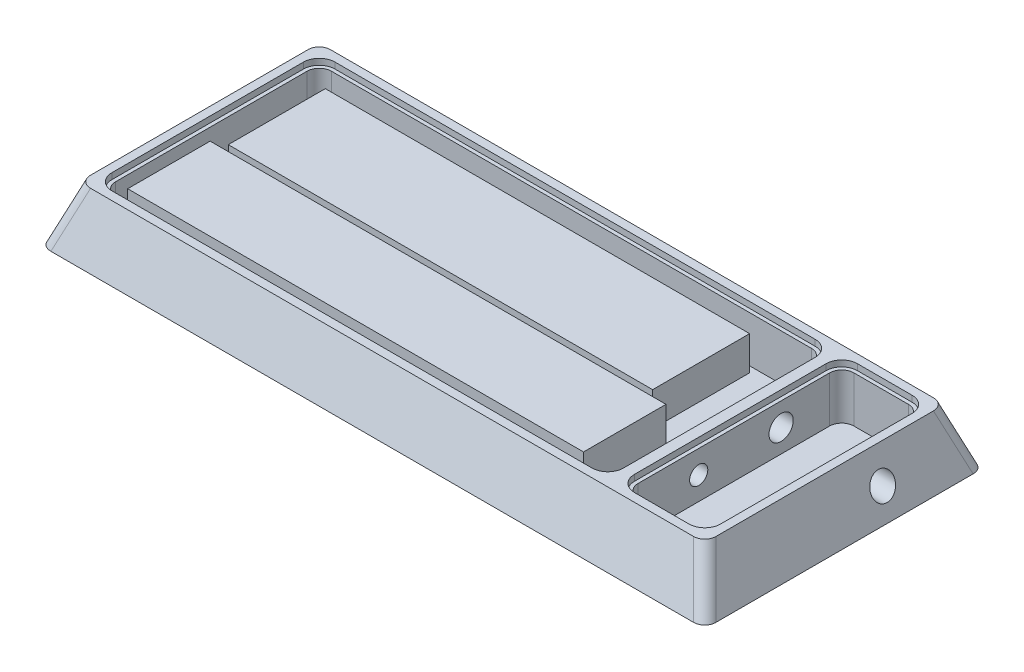
SolidWorks part; units mm, degrees
ref_plane "Front Plane" through (0, 0, 0) normal (0, 0, 1) x (1, 0, 0)
ref_plane "Top Plane" through (0, 0, 0) normal (0, 1, 0) x (1, 0, 0)
ref_plane "Right Plane" through (0, 0, 0) normal (1, 0, 0) x (0, 0, -1)
sketch "Sketch2" plane through (0, 0, 0) normal (0, 1, 0) x (1, 0, 0)
  line L0 (168, -89) -> (168, 89)
  line L1 (-248, -89) -> (168, -89)
  line L2 (-248, -89) -> (-248, 89)
  line L3 (-248, 89) -> (168, 89)
  line L4 (248, -89) -> (248, 89)
  line L5 (-248, -89) -> (248, 89) construction
  line L6 (-248, 89) -> (248, -89) construction
  line L7 (-238, -79) -> (138, -79)
  line L8 (-238, -79) -> (-238, -11)
  line L9 (-238, -11) -> (138, -11)
  line L10 (138, -79) -> (138, -11)
  line L11 (-238, 4) -> (112, 4)
  line L12 (-238, 4) -> (-238, 84)
  line L13 (-238, 84) -> (112, 84)
  line L14 (112, 4) -> (112, 84)
  line L15 (-258, 99) -> (258, 99)
  line L16 (258, -99) -> (258, 99)
  line L17 (-258, -99) -> (258, -99)
  line L18 (-258, -99) -> (-258, 99)
  line L19 (183, -89) -> (183, 89)
  line L20 (183, 89) -> (248, 89)
  line L21 (-248, 89) -> (248, 89) construction
  line L22 (183, -89) -> (248, -89)
  line L23 (-248, -89) -> (248, -89) construction
  point P0 (0, 0)
  point P14 (-238, -45)
  point P15 (-238, 44)
  dimension "D1" = 178
  dimension "D3" = 376
  dimension "D4" = 68
  dimension "D5" = 350
  dimension "D6" = 80
  dimension "D7" = 10
  dimension "D8" = 10
  dimension "D9" = 15
  dimension "D2" = 416
  dimension "D10" = 80
  dimension "D11" = 10
  dimension "D12" = 15
extrude "Boss-Extrude2" add sketch "Sketch2" along normal blind 45 contours L18 L17 L16 L15 L22 L19 L20 L4 L2 L3 L0 L1 region at (0, 0, -93.4732)
draft "Draft3" type of draft neutral plane draft angle 20 faces to draft 4 face at (0, 22.5, -99) face at (258, 22.5, 0) face at (0, 22.5, 99) face at (-258, 22.5, 0) neutral plane through (0, 45, 0) neutral plane normal (0, 1, 0) parameters "D1"=20
fillet "Fillet1" radius 10 12 edges at (-248, 22.5, 89) (168, 22.5, 89) (168, 22.5, -89) (-248, 22.5, -89) (-266.1893, 22.5, -107.1893) (266.1893, 22.5, -107.1893) (266.1893, 22.5, 107.1893) (248, 22.5, 89) (248, 22.5, -89) (183, 22.5, -89) (183, 22.5, 89) (-266.1893, 22.5, 107.1893)
extrude "Boss-Extrude3" add sketch "Sketch2<3>" along normal blind 2 contours L3 L2 L1 L0 L14 L11 L12 L13 L10 L7 L8 L9 | L7 L10 L9 L8 | L11 L14 L13 L12 | L19 L22 L4 L20 region at (3.9297, 0, 3.9766) region at (215.5, 0, 0) region at (-50, 0, 45) region at (-63, 0, -44)
sketch "Sketch2<3>" plane through (0, 0, 0) normal (0, 1, 0) x (1, 0, 0) same geometry as "Sketch2"
sketch "Sketch3" plane through (0, 45, 0) normal (0, 1, 0) x (1, 0, 0)
  line L12 (171, -79) -> (171, 79)
  line L13 (-238, -92) -> (158, -92)
  line L14 (-251, 79) -> (-251, -79)
  line L15 (158, 92) -> (-238, 92)
  line L16 (171, -79) -> (171, 79)
  line L17 (-238, -92) -> (158, -92)
  line L18 (-251, 79) -> (-251, -79)
  line L19 (158, 92) -> (-238, 92)
  line L24 (193, -92) -> (238, -92)
  line L25 (180, 79) -> (180, -79)
  line L26 (238, 92) -> (193, 92)
  line L27 (251, -79) -> (251, 79)
  line L28 (193, -92) -> (238, -92)
  line L29 (180, 79) -> (180, -79)
  line L30 (238, 92) -> (193, 92)
  line L31 (251, -79) -> (251, 79)
  arc A8 (158, -92) -> (171, -79) centre (158, -79) ccw
  arc A9 (171, 79) -> (158, 92) centre (158, 79) ccw
  arc A10 (-251, -79) -> (-238, -92) centre (-238, -79) ccw
  arc A11 (-238, 92) -> (-251, 79) centre (-238, 79) ccw
  arc A12 (158, -92) -> (171, -79) centre (158, -79) ccw
  arc A13 (171, 79) -> (158, 92) centre (158, 79) ccw
  arc A14 (-251, -79) -> (-238, -92) centre (-238, -79) ccw
  arc A15 (-238, 92) -> (-251, 79) centre (-238, 79) ccw
  arc A20 (180, -79) -> (193, -92) centre (193, -79) ccw
  arc A21 (193, 92) -> (180, 79) centre (193, 79) ccw
  arc A22 (251, 79) -> (238, 92) centre (238, 79) ccw
  arc A23 (238, -92) -> (251, -79) centre (238, -79) ccw
  arc A24 (180, -79) -> (193, -92) centre (193, -79) ccw
  arc A25 (193, 92) -> (180, 79) centre (193, 79) ccw
  arc A26 (251, 79) -> (238, 92) centre (238, 79) ccw
  arc A27 (238, -92) -> (251, -79) centre (238, -79) ccw
  dimension "D1" = 3
  dimension "D2" = 3
extrude "Cut-Extrude1" cut sketch "Sketch3" against normal blind 5
extrude "Boss-Extrude4" add sketch "Sketch2<5>" along normal blind 40 contours L7 L10 L9 L8 region at (-50, 0, 45)
sketch "Sketch2<5>" plane through (0, 0, 0) normal (0, 1, 0) x (1, 0, 0) same geometry as "Sketch2"
extrude "Boss-Extrude5" add sketch "Sketch2<6>" along normal blind 30 contours L11 L14 L13 L12 region at (-63, 0, -44)
sketch "Sketch2<6>" plane through (0, 0, 0) normal (0, 1, 0) x (1, 0, 0) same geometry as "Sketch2"
sketch "Sketch4" plane through (248, 0, 0) normal (-1, 0, 0) x (0, 0, 1)
  line L0 (-79, 40) -> (-79, 2) construction
  circle A0 centre (-39, 21) radius 10
  point P4 (-79, 21)
  dimension "D1" = 20
  dimension "D2" = 40
extrude "Cut-Extrude2" cut sketch "Sketch4" along normal up to surface (80 mm away) and the other way blind 54 from offset 0 up to face at (168, 21, 0)
sketch "Sketch5" plane through (183, 0, 0) normal (1, 0, 0) x (0, 0, -1)
  line L0 (-79, 40) -> (-79, 2) construction
  circle A0 centre (-29, 21) radius 7.5
  point P4 (-79, 21)
  dimension "D1" = 15
  dimension "D2" = 50
extrude "Cut-Extrude3" cut sketch "Sketch5" against normal up to surface (15 mm away) up to face at (168, 21, -29)
equation "\"D1@Sketch2\"=\"D8@Sketch2\"+\"D4@Sketch2\"+\"D9@Sketch2\"+\"D6@Sketch2\"+5"
equation "\"D2@Sketch2\"=\"D7@Sketch2\"+\"D3@Sketch2\"+30"
